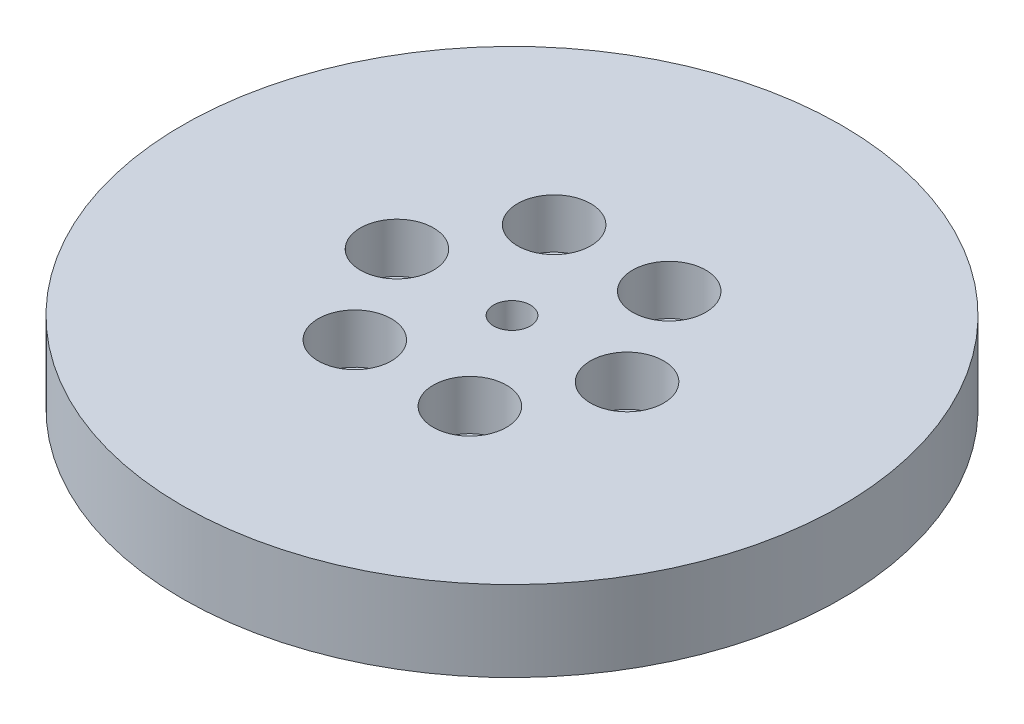
SolidWorks part; units mm, degrees
ref_plane "Front Plane" through (0, 0, 0) normal (0, 0, 1) x (1, 0, 0)
ref_plane "Top Plane" through (0, 0, 0) normal (0, 1, 0) x (1, 0, 0)
ref_plane "Right Plane" through (0, 0, 0) normal (1, 0, 0) x (0, 0, -1)
sketch "Sketch1" plane through (0, 0, 0) normal (0, 1, 0) x (1, 0, 0)
  circle A0 centre (0, 0) radius 90
  dimension "FLANGE_OD" = 180
extrude "Boss-Extrude1" add sketch "Sketch1" along normal blind 22
sketch "Sketch2" plane through (0, 0, 0) normal (0, 1, 0) x (1, 0, 0)
  circle A0 centre (0, 0) radius 5
  dimension "BORE_D" = 10
extrude "Cut-Extrude1" cut sketch "Sketch2" along normal through all
sketch "Sketch3" plane through (0, 22, 0) normal (0, 1, 0) x (1, 0, 0)
  circle A0 centre (0, 0) radius 31.4275 construction
  circle A1 centre (-31.4275, 0) radius 10
  dimension "BOLT_D" = 20
  dimension "BOLT_PCD" = 62.8551
extrude "Cut-Extrude2" cut sketch "Sketch3" against normal blind 13.5524
pattern_circular "CirPattern1" count 6 over 360 about axis through (0, 0, 0) along (0, 1, 0) of "Cut-Extrude2"
